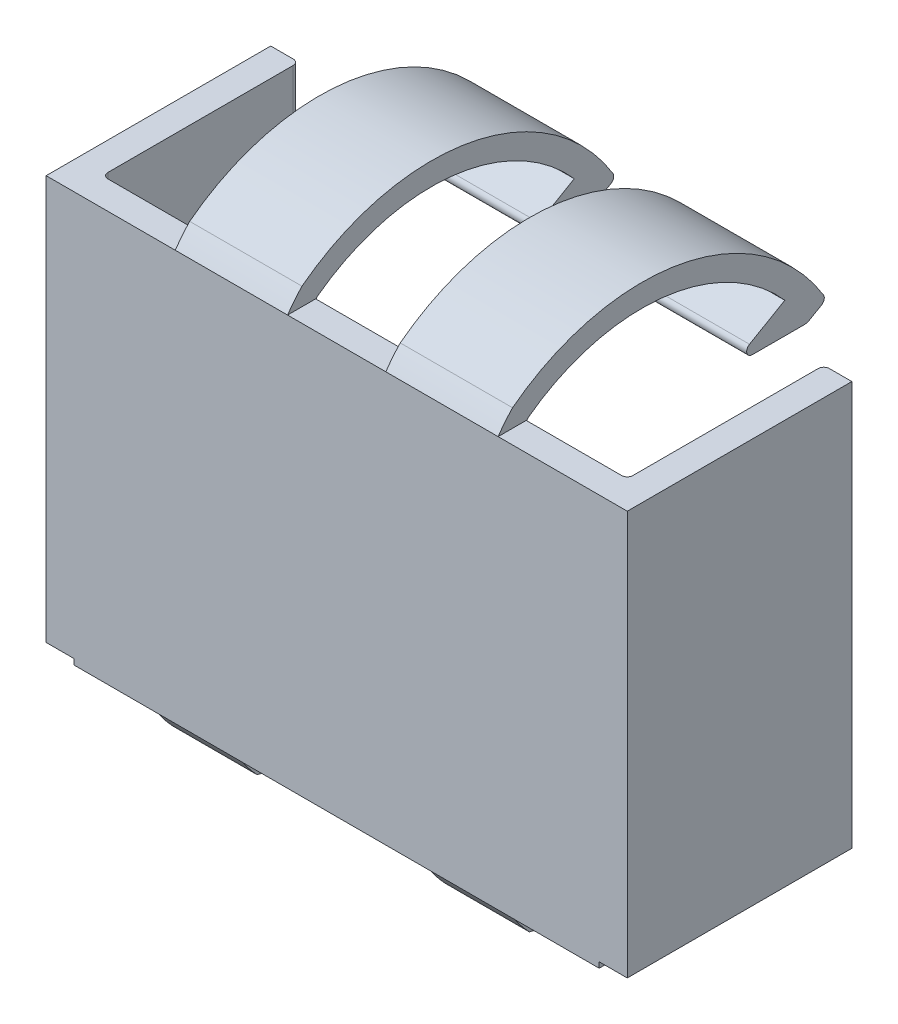
SolidWorks part; units mm, degrees
note: The reader was unsure of these and kept them because the rebuilt part matched: shared geometry of "Sketch2<5>".
ref_plane "Front Plane" through (0, 0, 0) normal (0, 0, 1) x (1, 0, 0)
ref_plane "Top Plane" through (0, 0, 0) normal (0, 1, 0) x (1, 0, 0)
ref_plane "Right Plane" through (0, 0, 0) normal (1, 0, 0) x (0, 0, -1)
sketch "Sketch1" plane through (0, 0, 0) normal (0, 0, 1) x (1, 0, 0)
  line L1 (-46.75, 36.5) -> (46.75, 36.5)
  line L2 (-46.75, 36.5) -> (-46.75, -36.5)
  line L3 (-46.75, -36.5) -> (46.75, -36.5)
  line L4 (46.75, 36.5) -> (46.75, -36.5)
  line L5 (-46.75, 36.5) -> (46.75, -36.5) construction
  line L6 (-46.75, -36.5) -> (46.75, 36.5) construction
  point P0 (0, 0)
  dimension "D1" = 93.5
  dimension "D2" = 73
extrude "Boss-Extrude1" add sketch "Sketch1" along normal blind 5
sketch "Sketch2" plane through (46.75, 0, 0) normal (1, 0, 0) x (0, 0, -1)
  line L0 (0, 26.5) -> (50, 26.5) construction
  line L1 (0, -36.5) -> (0, 36.5) construction
  line L2 (0, 43.5) -> (52, 43.5) construction
  line L5 (-5, 36.5) -> (0, 36.5)
  line L12 (-2.4348, 39.6736) -> (0, 36.5)
  line L13 (0, -36.5) -> (0, 36.0022)
  line L14 (-5, 36.5) -> (0, 36.0022)
  line L15 (50.4628, 26.7659) -> (52.5893, 27.988)
  line L16 (46.0603, 32) -> (39.7661, 28.366)
  line L17 (40.2661, 26.5) -> (49.4663, 26.5)
  line L18 (0, 0) -> (72.529, 0) construction
  line L20 (-2.5, -36.5) -> (-2.5, -43.5) construction
  line L22 (-5, -36.5) -> (0, -36.0022)
  line L23 (-2.4348, -39.6736) -> (0, -36.5)
  line L24 (-5, -36.5) -> (0, -36.5) construction
  line L25 (-2.5, -43.5) -> (57.8, -43.5) construction
  line L26 (50, -43.5) -> (50, -46.5)
  arc A0 (0.4032, 36.8046) -> (50, 26.5) centre (20.6237, 9.6187) cw
  arc A1 (-2.4348, 39.6736) -> (52.9443, 29.3766) centre (20.6237, 9.6187) cw
  arc A2 (0, 36.5) -> (50, 26.5) centre (20.6237, 9.6187) cw construction
  arc A3 (-2.4348, 39.6736) -> (53.4681, 28.493) centre (20.6237, 9.6187) cw construction
  arc A7 (0.4032, 36.8046) -> (0, 36.0022) centre (1, 36.0022) ccw
  arc A8 (-5, 36.5) -> (-2.4348, 39.6736) centre (15.6606, 22.4238) cw
  arc A9 (-5, -36.5) -> (-2.4348, -39.6736) centre (15.6606, -22.4238) ccw
  arc A12 (0.4032, -36.8046) -> (0, -36.0022) centre (1, -36.0022) cw
  arc A15 (0.4032, -36.8046) -> (50, -43.5) centre (52.2245, 160.0221) ccw
  arc A16 (-2.4348, -39.6736) -> (50, -46.5) centre (49.836, 157.0342) ccw
  arc A17 (40.2661, 26.5) -> (39.7661, 28.366) centre (40.2661, 27.5) cw
  arc A18 (50.4628, 26.7659) -> (49.4663, 26.5) centre (49.4663, 28.5) cw
  arc A19 (52.9443, 29.3766) -> (52.5893, 27.988) centre (52.0911, 28.855) cw
  point P26 (46.0603, 32)
  point P38 (36.5341, 26.5)
  dimension "D8" = 25
  dimension "D9" = 7
  dimension "D10" = 1
  dimension "D11" = 203.5342
  dimension "D12" = 3
  dimension "D13" = 1
  dimension "D14" = 2
  dimension "D15" = 1
  dimension "D1" = 50
  dimension "D2" = 10
  dimension "D3" = 7
  dimension "D4" = 52
  dimension "D6" = 30
  dimension "D7" = 5.5
  dimension "D16" = 2.4527
  dimension "D5" = 4
extrude "Boss-Extrude3" add sketch "Sketch2" against normal blind 20 from offset 18 offset against normal yes
mirror "Mirror1" about plane through (0, 0, 0) normal (1, 0, 0) of "Boss-Extrude3"
sketch "Sketch3" plane through (46.75, 0, 0) normal (1, 0, 0) x (0, 0, -1)
  line L1 (-5, 36.5) -> (35, 36.5)
  line L2 (-5, 36.5) -> (-5, -35.5)
  line L3 (-5, -35.5) -> (35, -35.5)
  line L4 (35, 36.5) -> (35, -35.5)
  dimension "D1" = 40
  dimension "D2" = 72
extrude "Boss-Extrude4" add sketch "Sketch3" along normal blind 5
mirror "Mirror3" about plane through (0, 0, 0) normal (1, 0, 0) of "Boss-Extrude4"
fillet "Fillet2" radius 1 4 edges at (46.75, 0.5, -35) (-46.75, 0.5, -35) (-46.75, 0.5, 0) (46.75, 0.5, 0)
extrude "Boss-Extrude5" add sketch "Sketch2<5>" against normal blind 15 from offset 15 offset against normal yes
sketch "Sketch2<5>" plane through (46.75, 0, 0) normal (1, 0, 0) x (0, 0, -1) same geometry as "Sketch2"
mirror "Mirror4" about plane through (0, 0, 0) normal (1, 0, 0) of "Boss-Extrude5"
